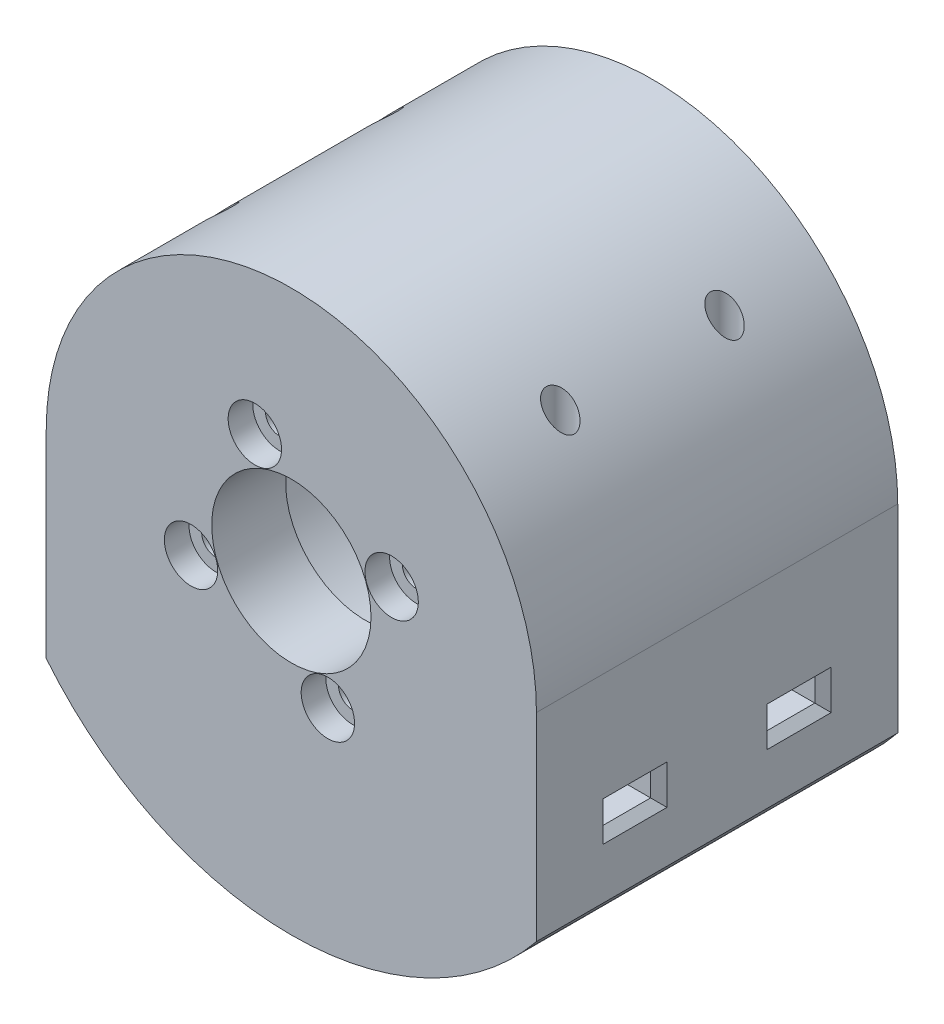
SolidWorks part; units mm, degrees
ref_plane "Front Plane" through (0, 0, 0) normal (0, 0, 1) x (1, 0, 0)
ref_plane "Top Plane" through (0, 0, 0) normal (0, 1, 0) x (1, 0, 0)
ref_plane "Right Plane" through (0, 0, 0) normal (1, 0, 0) x (0, 0, -1)
sketch "Sketch1" plane through (0, 0, 0) normal (0, 0, 1) x (1, 0, 0)
  line L0 (-29.85, 15.8435) -> (29.85, 15.8435)
  line L1 (-29.85, -24.1565) -> (29.85, -24.1565)
  line L2 (-29.85, -24.1565) -> (-29.85, 24.1565)
  line L3 (-29.85, 24.1565) -> (29.85, 24.1565)
  line L4 (29.85, -24.1565) -> (29.85, 24.1565)
  line L5 (-29.85, -24.1565) -> (29.85, 24.1565) construction
  line L6 (-29.85, 24.1565) -> (29.85, -24.1565) construction
  circle A0 centre (0, -11) radius 16.2
  circle A1 centre (0, 0) radius 38.4
  point P0 (0, 0)
  dimension "D2" = 32.4
  dimension "D4" = 76.8
  dimension "D1" = 59.7
  dimension "D3" = 11
  dimension "D5" = 40
extrude "Boss-Extrude1" add sketch "Sketch1" along normal blind 44 contours L1 A1 A0 | A0 L1 L4 L0 L2 | L1 A0 | L1 A0 region at (0, 15.1249, 0) region at (0, -30.2791, 0) region at (0, -10.2831, 0) region at (0, -25.3843, 0)
extrude "Cut-Extrude1" cut sketch "Sketch1<3>" along normal blind 35 contours L1 A0 | L1 A0 region at (0, -10.2831, 0) region at (0, -25.3843, 0)
sketch "Sketch1<3>" plane through (0, 0, 0) normal (0, 0, 1) x (1, 0, 0) same geometry as "Sketch1"
sketch "Sketch2" plane through (0, 0, 44) normal (0, 0, 1) x (1, 0, 0)
  circle A0 centre (0, -11) radius 9.7
  dimension "D1" = 19.4
extrude "Cut-Extrude2" cut sketch "Sketch2" against normal up to next
sketch "Sketch3" plane through (0, 0, 44) normal (0, 0, 1) x (1, 0, 0)
  line L0 (0, -11) -> (0, 2) construction
  line L1 (0, -11) -> (-4.4463, 1.216) construction
  circle A0 centre (0, -11) radius 13 construction
  point P4 (12.216, -6.5537)
  point P5 (4.4463, -23.216)
  point P6 (-4.4463, 1.216)
  point P10 (-12.216, -15.4463)
  dimension "D1" = 26
  dimension "D2" = 20
  dimension "D3" = 4
hole_wizard "CBORE for M3 SHCS1" positions "Sketch3" profile "Sketch4" counterbore size "M3" standard "ANSI Metric" end condition up to next
sketch "Sketch4" plane through (-12.216, -15.4463, 44) normal (1, 0, 0) x (0, -1, 0)
  line L0 (0, 0) -> (0, 9)
  line L1 (0, 9) -> (1.7, 9)
  line L3 (1.7, 9) -> (1.7, 3)
  line L4 (1.7, 3) -> (3.25, 3)
  line L5 (3.25, 3) -> (3.25, 0)
  line L7 (3.25, 0) -> (0, 0)
  line L11 (0, -6.35) -> (0, 107.95) construction
  dimension "Thru Hole Dia." = 3.4
  dimension "Thru Hole Depth" = 9
  dimension "C'Bore Dia." = 6.5
  dimension "C'Bore Depth" = 3
ref_plane "Plane1" through (0, -24.1565, 0) normal (0, 1, 0) x (1, 0, 0)
ref_plane "Plane2" through (0, -44.1565, 0) normal (0, -1, 0) x (-1, 0, 0)
sketch "Sketch6" plane through (0, -44.1565, 0) normal (0, -1, 0) x (-1, 0, 0)
  line L0 (0, 0) -> (0, -44) construction
  line L1 (-38.4, 0) -> (38.4, 0) construction
  line L2 (-29.85, -44) -> (29.85, -44) construction
  line L3 (29.85, -22) -> (-29.85, -22) construction
  line L4 (29.85, -44) -> (29.85, 0) construction
  line L5 (-29.85, -44) -> (-29.85, 0) construction
  circle A0 centre (20.75, -12) radius 1.7
  circle A1 centre (-20.75, -12) radius 1.7
  circle A2 centre (20.75, -32) radius 1.7
  circle A3 centre (-20.75, -32) radius 1.7
  dimension "D1" = 3.4
  dimension "D2" = 12
  dimension "D3" = 41.5
extrude "Cut-Extrude3" cut sketch "Sketch6" against normal up to next
ref_plane "Plane3" through (0, -14.1565, 0) normal (0, 1, 0) x (1, 0, 0)
sketch "Sketch7" plane through (0, -14.1565, 0) normal (0, 1, 0) x (1, 0, 0)
  line L0 (22.4243, -9.1) -> (22.4243, -14.9)
  line L1 (-19.0757, -9.1) -> (-22.4243, -9.1)
  line L2 (-22.4243, -9.1) -> (-24.0986, -12)
  line L3 (-24.0986, -12) -> (-22.4243, -14.9)
  line L4 (-22.4243, -14.9) -> (-19.0757, -14.9)
  line L5 (-19.0757, -14.9) -> (-17.4014, -12)
  line L6 (-17.4014, -12) -> (-19.0757, -9.1)
  line L8 (22.4243, -9.1) -> (29.85, -9.1)
  line L9 (22.4243, -14.9) -> (29.85, -14.9)
  line L10 (29.85, -9.1) -> (29.85, -14.9)
  line L11 (17.4014, -12) -> (19.0757, -14.9)
  line L12 (19.0757, -14.9) -> (22.4243, -14.9)
  line L13 (22.4243, -14.9) -> (24.0986, -12)
  line L14 (24.0986, -12) -> (22.4243, -9.1)
  line L15 (22.4243, -9.1) -> (19.0757, -9.1)
  line L16 (19.0757, -9.1) -> (17.4014, -12)
  line L17 (-22.4243, -29.1) -> (-24.0986, -32)
  line L18 (-24.0986, -32) -> (-22.4243, -34.9)
  line L19 (-22.4243, -34.9) -> (-19.0757, -34.9)
  line L20 (-19.0757, -34.9) -> (-17.4014, -32)
  line L21 (-17.4014, -32) -> (-19.0757, -29.1)
  line L22 (-19.0757, -29.1) -> (-22.4243, -29.1)
  line L23 (22.4243, -29.1) -> (19.0757, -29.1)
  line L24 (19.0757, -29.1) -> (17.4014, -32)
  line L25 (17.4014, -32) -> (19.0757, -34.9)
  line L26 (19.0757, -34.9) -> (22.4243, -34.9)
  line L27 (22.4243, -34.9) -> (24.0986, -32)
  line L28 (24.0986, -32) -> (22.4243, -29.1)
  line L30 (22.4243, -29.1) -> (22.4243, -34.9)
  line L32 (22.4243, -29.1) -> (29.85, -29.1)
  line L33 (22.4243, -34.9) -> (29.85, -34.9)
  line L34 (29.85, -29.1) -> (29.85, -34.9)
  line L35 (-22.4243, -34.9) -> (-22.4243, -29.1)
  line L36 (-22.4243, -34.9) -> (-29.85, -34.9)
  line L37 (-22.4243, -29.1) -> (-29.85, -29.1)
  line L38 (-29.85, -34.9) -> (-29.85, -29.1)
  line L39 (-22.4243, -14.9) -> (-22.4243, -9.1)
  line L40 (-22.4243, -14.9) -> (-29.85, -14.9)
  line L41 (-22.4243, -9.1) -> (-29.85, -9.1)
  line L42 (-29.85, -14.9) -> (-29.85, -9.1)
  line L45 (-29.85, -44) -> (-29.85, 0) construction
  line L46 (29.85, -44) -> (29.85, 0) construction
  circle A0 centre (-20.75, -12) radius 2.9 construction
  circle A1 centre (20.75, -12) radius 2.9 construction
  circle A2 centre (-20.75, -32) radius 2.9 construction
  circle A3 centre (20.75, -32) radius 2.9 construction
  dimension "D1" = 5.8
extrude "Cut-Extrude4" cut sketch "Sketch7" against normal blind 2.8 contours L42 L40 L3 L2 L41 | L3 L39 L2 | L39 L4 L5 L6 L1 | L38 L36 L18 L17 L37 | L18 L35 L17 | L35 L19 L20 L21 L22 | L30 L23 L24 L25 L26 | L34 L32 L28 L27 L33 | L28 L30 L27 | L14 L13 L9 L10 L8 | L13 L14 L0 | L15 L16 L11 L12 L0 region at (22.9824, -14.1565, 12) region at (26.538, -14.1565, 12) region at (20.3035, -14.1565, 12) region at (-20.3035, -14.1565, 12) region at (-22.9824, -14.1565, 12) region at (-26.538, -14.1565, 12) region at (-22.9824, -14.1565, 32) region at (-20.3035, -14.1565, 32) region at (-26.538, -14.1565, 32) region at (20.3035, -14.1565, 32) region at (26.538, -14.1565, 32) region at (22.9824, -14.1565, 32)
chamfer "Chamfer1" distance 1 angle 45 16 edges at (-29.85, -14.1565, 32) (-29.85, -15.5565, 29.1) (-29.85, -16.9565, 32) (-29.85, -15.5565, 34.9) (-29.85, -14.1565, 12) (-29.85, -15.5565, 9.1) (-29.85, -16.9565, 12) (-29.85, -15.5565, 14.9) (29.85, -15.5565, 29.1) (29.85, -14.1565, 32) (29.85, -15.5565, 34.9) (29.85, -16.9565, 32) (29.85, -15.5565, 9.1) (29.85, -14.1565, 12) (29.85, -15.5565, 14.9) (29.85, -16.9565, 12)
sketch "Sketch8" plane through (0, 0, 0) normal (0, 0, -1) x (-1, 0, 0)
  line L0 (17.4014, -16.9565) -> (17.4014, -14.1565) construction
  line L1 (17.4014, -16.9565) -> (17.4014, -14.1565) construction
  line L2 (-17.4014, -16.9565) -> (-17.4014, -14.1565) construction
  line L3 (-17.4014, -16.9565) -> (-17.4014, -14.1565) construction
  line L4 (-29.85, -13.1565) -> (-29.85, -17.9565) construction
  line L5 (-29.85, -13.1565) -> (-29.85, -17.9565) construction
  line L6 (29.85, -17.9565) -> (29.85, -13.1565) construction
  line L7 (29.85, -17.9565) -> (29.85, -13.1565) construction
  line L8 (29.85, -12.1565) -> (16.9014, -12.1565)
  line L9 (29.85, -24.1565) -> (29.85, 15.8435) construction
  line L10 (16.9014, -12.1565) -> (16.9014, 15.8435) construction
  line L11 (-29.85, -12.1565) -> (-16.9014, -12.1565)
  line L12 (0, 15.8435) -> (0, 0) construction
  line L13 (29.85, 15.8435) -> (-29.85, 15.8435) construction
  circle A0 centre (0, -11) radius 16.2 construction
  circle A1 centre (0, -11) radius 16.2 construction
  arc A2 (16.9014, -12.1565) -> (-16.9014, -12.1565) centre (0, -11) cw
  point P23 (0, -27.2)
  dimension "D1" = 1
  dimension "D2" = 0.5
split "Split1" trim tools "Sketch8" bodies to split 106 resulting bodies 108 109
move or copy body "Body-Move/Copy1" bodies to move or copy 108 copy no translate (0, -11, 0) parameters "D1"=0, "D2"=11, "D3"=0
sketch "Sketch9" plane through (0, 0, 0) normal (0, 0, -1) x (-1, 0, 0)
  line L0 (-16.9014, -23.1565) -> (-29.85, -23.1565) construction
  line L1 (29.85, -23.1565) -> (16.9014, -23.1565) construction
  line L2 (29.85, -12.1565) -> (16.9014, -12.1565) construction
  line L3 (-16.9014, -12.1565) -> (-29.85, -12.1565) construction
  line L4 (-16.9014, -23.1565) -> (-29.85, -23.1565)
  line L5 (29.85, -23.1565) -> (16.9014, -23.1565)
  line L6 (29.85, -12.1565) -> (16.9014, -12.1565)
  line L7 (-16.9014, -12.1565) -> (-29.85, -12.1565)
  line L8 (29.85, -23.1565) -> (29.85, -12.1565)
  line L9 (-29.85, -12.1565) -> (-29.85, -23.1565)
  arc A0 (-16.9014, -23.1565) -> (16.9014, -23.1565) centre (0, -22) ccw construction
  arc A1 (-16.9014, -12.1565) -> (16.9014, -12.1565) centre (0, -11) ccw construction
  arc A2 (-16.9014, -23.1565) -> (16.9014, -23.1565) centre (0, -22) ccw
  arc A3 (-16.9014, -12.1565) -> (16.9014, -12.1565) centre (0, -11) ccw
extrude "Boss-Extrude2" add sketch "Sketch9" against normal up to surface (44 mm away) up to face at (0, -32.1612, 44)
sketch "Sketch10" plane through (0, -12.1565, 0) normal (0, 1, 0) x (1, 0, 0)
  circle A0 centre (20.75, -32) radius 1.7 construction
  circle A1 centre (-20.75, -32) radius 1.7 construction
  circle A2 centre (-20.75, -12) radius 1.7 construction
  circle A3 centre (20.75, -12) radius 1.7 construction
  circle A4 centre (20.75, -32) radius 1.7
  circle A5 centre (-20.75, -32) radius 1.7
  circle A6 centre (-20.75, -12) radius 1.7
  circle A7 centre (20.75, -12) radius 1.7
extrude "Cut-Extrude5" cut sketch "Sketch10" against normal through all
sketch "Sketch11" plane through (0, 0, 0) normal (0, 0, -1) x (-1, 0, 0)
  line L2 (-29.85, -35.1565) -> (-29.85, 15.8435) construction
  circle A0 centre (0, -11) radius 16.2 construction
  circle A1 centre (0, -11) radius 16.2
  circle A2 centre (0, -11) radius 29.85 construction
  arc A3 (-29.85, -11) -> (29.85, -11) centre (0, -11) cw
  line M10 (29.85, -35.1565) -> (29.85, 15.8435)
  line M11 (29.85, 15.8435) -> (-29.85, 15.8435)
  line M12 (-29.85, 15.8435) -> (-29.85, -35.1565)
extrude "Cut-Extrude6" cut sketch "Sketch11" against normal through all contours A3 M12 M11 | A3 M11 M10 region at (25.2027, 9.5658, 0) region at (-25.2027, 9.5658, 0)
sketch "Sketch12" plane through (0, 0, 0) normal (0, 0, -1) x (-1, 0, 0)
  line L0 (13.0557, 15.8435) -> (-13.0557, 15.8435)
  arc A0 (-13.0557, 15.8435) -> (13.0557, 15.8435) centre (0, -11) cw
  circle A2 centre (0, -11) radius 16.2 construction
extrude "Boss-Extrude3" add sketch "Sketch12" against normal up to surface (44 mm away) up to face at (15.466, -6.5537, 44)
